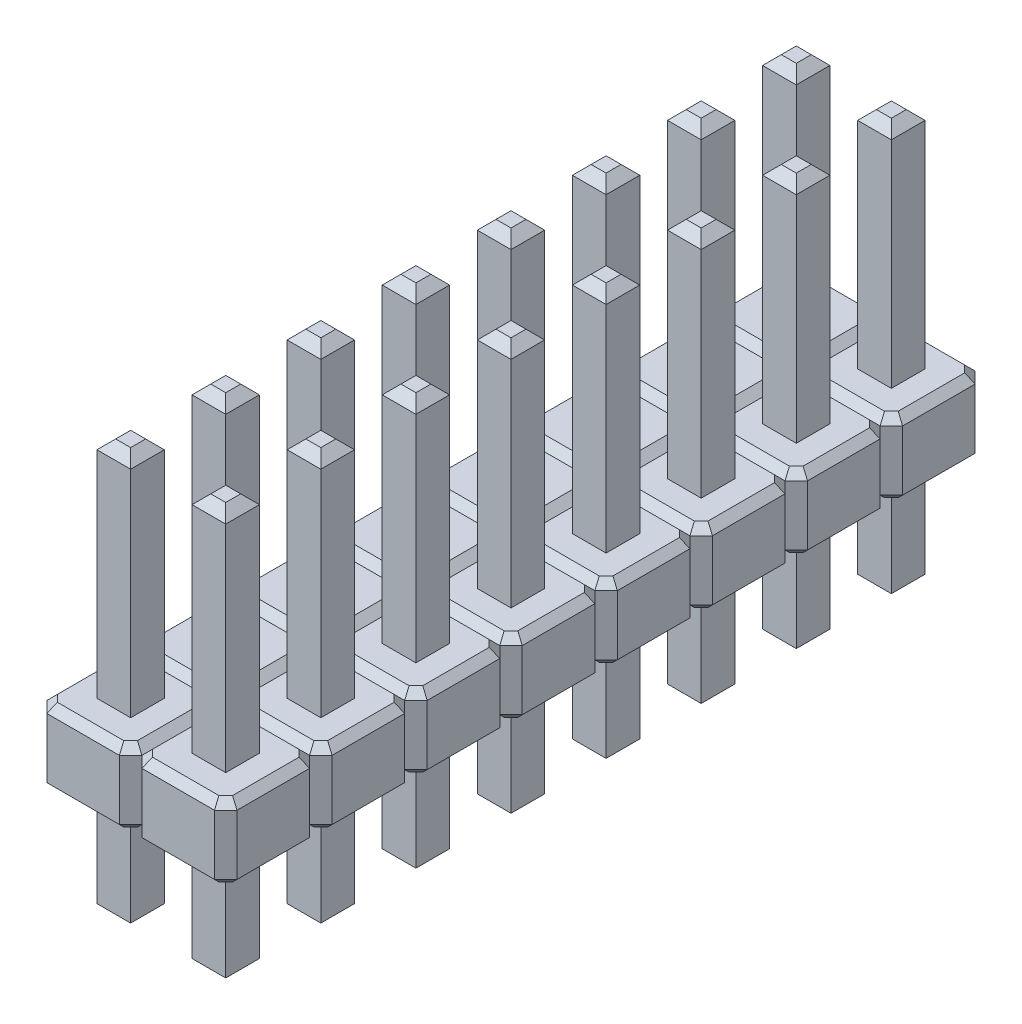
SolidWorks part; units mm, degrees
note: The reader was unsure of these and kept them because the rebuilt part matched: shared geometry of "Эскиз1<3>".
other "PIN4"
other "PIN2"
other "PIN5"
other "PIN3"
other "PIN1"
other "PIN6" parameters "D1"=27.9408, "D4"=1.6296, "D5"=1.1205, "D9"=0.3, "D10"=0.3, "D11"=0.3, "D12"=0.3, "D8"=0.5
ref_plane "Спереди" through (0, 0, 0) normal (0, 0, 1) x (1, 0, 0)
ref_plane "Сверху" through (0, 0, 0) normal (0, 1, 0) x (1, 0, 0)
ref_plane "Справа" through (0, 0, 0) normal (1, 0, 0) x (0, 0, -1)
sketch "Эскиз1" plane through (0, 0, 0) normal (0, 1, 0) x (1, 0, 0)
  line L1 (-0.45, -0.45) -> (0.45, -0.45)
  line L2 (-0.45, -0.45) -> (-0.45, 0.45)
  line L3 (-0.45, 0.45) -> (0.45, 0.45)
  line L4 (0.45, -0.45) -> (0.45, 0.45)
  line L5 (-0.45, -0.45) -> (0.45, 0.45) construction
  line L6 (-0.45, 0.45) -> (0.45, -0.45) construction
  line L26 (0.97, -1.27) -> (1.27, -0.97)
  line L27 (-0.97, -1.27) -> (0.97, -1.27)
  line L28 (-1.27, -0.97) -> (-1.27, 0.97)
  line L29 (-0.97, 1.27) -> (0.97, 1.27)
  line L30 (1.27, -0.97) -> (1.27, 0.97)
  line L31 (-1.27, -1.27) -> (1.27, 1.27) construction
  line L32 (-1.27, 1.27) -> (1.27, -1.27) construction
  line L33 (-0.97, -1.27) -> (-1.27, -0.97)
  line L34 (-1.27, 0.97) -> (-0.97, 1.27)
  line L35 (1.27, 0.97) -> (0.97, 1.27)
  circle A0 centre (0, 0) radius 0.45 construction
  dimension "D1" = 0.9
  dimension "D4" = 1.27
  dimension "D5" = 1.27
extrude "metal part" add sketch "Эскиз1" along normal blind 11 contours L1 L4 L3 L2
extrude "plastic part" add sketch "Эскиз1<3>" along direction (0, -1, 0) on the side of the normal blind 2 from offset 3 separate body contours L30 L35 L29 L34 L28 L33 L27 L26 L4 L1 L2 L3
sketch "Эскиз1<3>" plane through (0, 0, 0) normal (0, 1, 0) x (1, 0, 0) same geometry as "Эскиз1"
chamfer "Фаска1" distance 0.2 angle 45 16 edges at (1.12, 3, -1.12) (1.27, 3, 0) (1.12, 3, 1.12) (0, 3, 1.27) (-1.12, 3, 1.12) (-1.27, 3, 0) (-1.12, 3, -1.12) (0, 3, -1.27) (1.12, 5, -1.12) (0, 5, -1.27) (-1.12, 5, -1.12) (-1.27, 5, 0) (-1.12, 5, 1.12) (1.27, 5, 0) (1.12, 5, 1.12) (0, 5, 1.27) tangent propagation no
chamfer "Фаска2" distance 0.25 angle 45 8 edges at (0, 0, 0.45) (0.45, 0, 0) (0, 0, -0.45) (-0.45, 0, 0) (0.45, 11, 0) (0, 11, -0.45) (0, 11, 0.45) (-0.45, 11, 0)
pattern_linear "Линейный массив1" count 8 spacing 2.54 along (0, 0, -1) count 2 spacing 2.54 along (1, 0, 0) of bodies 104 103
combine bodies "Соединить2" operation type add bodies to combine 113 122 123 114 104 121 124 115 125 116 126 117 127 119 128 120
equation "\"D5@Эскиз1\"=\"D4@Эскиз1\""
